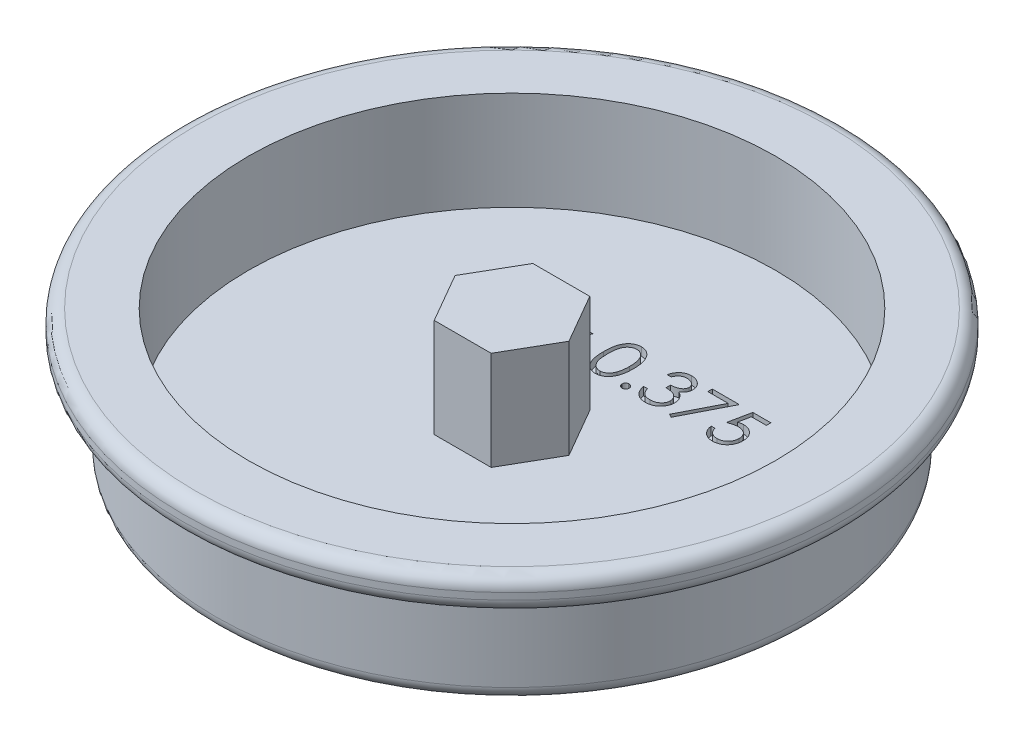
SolidWorks part; units mm, degrees
ref_plane "Front Plane" through (0, 0, 0) normal (0, 0, 1) x (1, 0, 0)
ref_plane "Top Plane" through (0, 0, 0) normal (0, 1, 0) x (1, 0, 0)
ref_plane "Right Plane" through (0, 0, 0) normal (1, 0, 0) x (0, 0, -1)
sketch "Sketch1" plane through (0, 0, 0) normal (0, 0, 1) x (1, 0, 0)
  line L0 (0, 0) -> (27.305, 0)
  line L1 (28.575, 1.27) -> (28.575, 8.255)
  line L2 (29.845, 9.525) -> (30.48, 9.525)
  line L3 (31.75, 10.795) -> (31.75, 11.43)
  line L4 (30.48, 12.7) -> (25.4, 12.7)
  line L5 (25.4, 12.7) -> (25.4, 3.175)
  line L6 (25.4, 3.175) -> (0, 3.175)
  line L7 (0, 3.175) -> (0, 0)
  arc A0 (31.75, 11.43) -> (30.48, 12.7) centre (30.48, 11.43) ccw
  arc A1 (30.48, 9.525) -> (31.75, 10.795) centre (30.48, 10.795) ccw
  arc A2 (28.575, 8.255) -> (29.845, 9.525) centre (29.845, 8.255) cw
  arc A3 (27.305, 0) -> (28.575, 1.27) centre (27.305, 1.27) ccw
  point P3 (0, 1.5875)
  dimension "D7" = 1.27
  dimension "D1" = 3.175
  dimension "D2" = 3.175
  dimension "D3" = 3.175
  dimension "D4" = 6.35
  dimension "D5" = 25.4
  dimension "D6" = 9.525
revolve "Revolve1" add sketch "Sketch1" angle 360 about L7
sketch "Sketch2" plane through (0, 3.175, 0) normal (0, 1, 0) x (1, 0, 0)
  line L1 (2.7423, 4.7498) -> (-2.7423, 4.7498)
  line L2 (-2.7423, 4.7498) -> (-5.4846, 0)
  line L3 (-5.4846, 0) -> (-2.7423, -4.7498)
  line L4 (-2.7423, -4.7498) -> (2.7423, -4.7498)
  line L5 (2.7423, -4.7498) -> (5.4846, 0)
  line L6 (5.4846, 0) -> (2.7423, 4.7498)
  circle A0 centre (0, 0) radius 4.7498 construction
  dimension "D1" = 9.4996
extrude "Boss-Extrude1" add sketch "Sketch2" along normal blind 9.525
sketch "Sketch3" plane through (0, 3.175, 0) normal (0, 1, 0) x (1, 0, 0)
  text T0 "2 x 0.375" font "Century Gothic" height in points 16
extrude "Cut-Extrude1" cut sketch "Sketch3" against normal blind 0.7937
